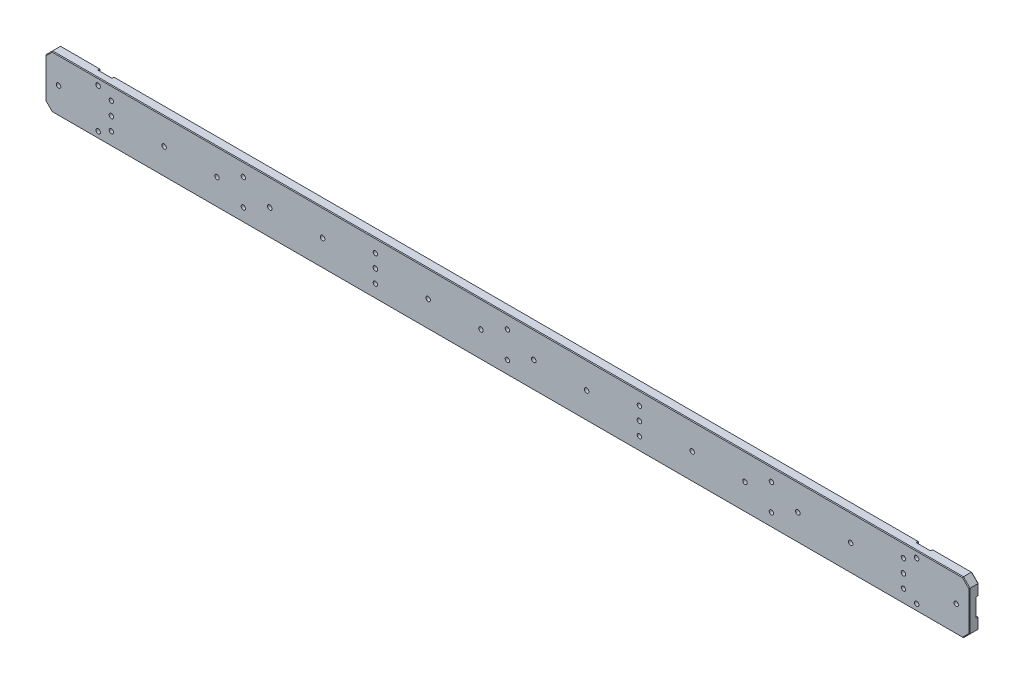
SolidWorks part; units mm, degrees
ref_plane "前视基准面" through (0, 0, 0) normal (0, 0, 1) x (1, 0, 0)
ref_plane "上视基准面" through (0, 0, 0) normal (0, 1, 0) x (1, 0, 0)
ref_plane "右视基准面" through (0, 0, 0) normal (1, 0, 0) x (0, 0, -1)
sketch "草图1" plane through (0, 0, 0) normal (0, 0, 1) x (1, 0, 0)
  line L1 (-700, 40) -> (700, 40)
  line L2 (-700, 40) -> (-700, -40)
  line L3 (-700, -40) -> (700, -40)
  line L4 (700, 40) -> (700, -40)
  line L5 (-700, 40) -> (700, -40) construction
  line L6 (-700, -40) -> (700, 40) construction
  point P0 (0, 0)
  dimension "D1" = 1400
  dimension "D2" = 80
extrude "凸台-拉伸1" add sketch "草图1" along normal blind 14
sketch "草图2" plane through (0, 0, 0) normal (0, 0, -1) x (-1, 0, 0)
  line L1 (750, -14) -> (-750, -14)
  line L2 (750, -14) -> (750, 14)
  line L3 (750, 14) -> (-750, 14)
  line L4 (-750, -14) -> (-750, 14)
  line L5 (750, -14) -> (-750, 14) construction
  line L6 (750, 14) -> (-750, -14) construction
  point P0 (0, 0)
  dimension "D1" = 28
  dimension "D2" = 1500
extrude "切除-拉伸1" cut sketch "草图2" against normal blind 4
hole_wizard "打孔尺寸(%根据)内六角圆柱头螺钉的类型1" positions "草图4" profile "草图6" counterbore size "M6" standard "GB" end condition through all
sketch "草图4" plane through (0, 0, 0) normal (0, 0, -1) x (-1, 0, 0)
  line L0 (0, -20) -> (0, 20) construction
  point P0 (0, -20)
  point P1 (0, 20)
  point P4 (0, 0)
  dimension "D1" = 40
sketch "草图6" plane through (0, -20, 0) normal (1, 0, 0) x (0, 1, 0)
  line L0 (0, 0) -> (0, 14)
  line L1 (0, 14) -> (3.3, 14)
  line L3 (3.3, 14) -> (3.3, 8)
  line L4 (3.3, 8) -> (5.5, 8)
  line L5 (5.5, 8) -> (5.5, 0)
  line L7 (5.5, 0) -> (0, 0)
  line L11 (0, -6.35) -> (0, 107.95) construction
  dimension "通孔孔直径" = 6.6
  dimension "通孔孔深度" = 14
  dimension "柱形沉头孔直径" = 11
  dimension "柱形沉头孔深度" = 8
pattern_linear "阵列(线性)1" count 4 spacing 200 along (1, 0, 0) count 4 spacing 200 along (-1, 0, 0) of "打孔尺寸(%根据)内六角圆柱头螺钉的类型1"
hole_wizard "M8 螺纹孔1" positions "草图7" profile "草图8" tap size "M8" standard "GB" end condition through all
sketch "草图7" plane through (0, 0, 4) normal (0, 0, -1) x (-1, 0, 0)
  point P0 (-680, 0)
sketch "草图8" plane through (680, 0, 4) normal (1, 0, 0) x (0, 1, 0)
  line L0 (0, 0) -> (0, 10)
  line L1 (0, 10) -> (3.4, 10)
  line L2 (3.4, 10) -> (3.4, 0)
  line L5 (3.4, 0) -> (0, 0)
  line L11 (0, -6.35) -> (0, 107.95) construction
  dimension "通孔螺纹孔钻头直径" = 6.8
  dimension "通孔螺纹孔钻头深度" = 10
cosmetic thread "孔螺蚊线1" parameters "D2"=8
pattern_linear "阵列(线性)2" count 18 spacing 80 along (-1, 0, 0) of "M8 螺纹孔1"
cosmetic thread "孔螺蚊线2" parameters "D2"=8
cosmetic thread "孔螺蚊线3" parameters "D2"=8
cosmetic thread "孔螺蚊线4" parameters "D2"=8
cosmetic thread "孔螺蚊线5" parameters "D2"=8
cosmetic thread "孔螺蚊线6" parameters "D2"=8
cosmetic thread "孔螺蚊线7" parameters "D2"=8
cosmetic thread "孔螺蚊线8" parameters "D2"=8
cosmetic thread "孔螺蚊线9" parameters "D2"=8
cosmetic thread "孔螺蚊线10" parameters "D2"=8
cosmetic thread "孔螺蚊线11" parameters "D2"=8
cosmetic thread "孔螺蚊线12" parameters "D2"=8
cosmetic thread "孔螺蚊线13" parameters "D2"=8
cosmetic thread "孔螺蚊线14" parameters "D2"=8
cosmetic thread "孔螺蚊线15" parameters "D2"=8
cosmetic thread "孔螺蚊线16" parameters "D2"=8
cosmetic thread "孔螺蚊线17" parameters "D2"=8
cosmetic thread "孔螺蚊线18" parameters "D2"=8
chamfer "倒角1" distance 10 angle 45 4 edges at (-700, -40, 7) (-700, 40, 7) (700, -40, 7) (700, 40, 7)
chamfer "倒角2" distance 1 angle 45 20 edges at (695, 35, 14) (0, 40, 14) (-695, 35, 14) (-700, 0, 14) (-695, -35, 14) (0, -40, 14) (695, -35, 14) (700, 0, 14) (695, -35, 0) (700, -22, 0) (0, -40, 0) (-695, -35, 0) (-700, -22, 0) (0, -14, 0) (-695, 35, 0) (-700, 22, 0) (0, 14, 0) (700, 22, 0) (695, 35, 0) (0, 40, 0)
sketch "草图9" plane through (0, -40, 0) normal (0, -1, 0) x (1, 0, 0)
  line L0 (689.5858, 0) -> (-689.5858, 0) construction
  line L1 (-610, -3) -> (-630, -3)
  line L2 (-610, -3) -> (-610, 3)
  line L3 (-610, 3) -> (-630, 3)
  line L4 (-630, -3) -> (-630, 3)
  line L5 (-610, -3) -> (-630, 3) construction
  line L6 (-610, 3) -> (-630, -3) construction
  line L7 (-700, 1) -> (-700, 13) construction
  point P0 (-620, 0)
  dimension "D1" = 20
  dimension "D2" = 70
  dimension "D3" = 3
extrude "切除-拉伸2" cut sketch "草图9" against normal through all
hole_wizard "M8 螺纹孔2" positions "草图10" profile "草图11" tap size "M8" standard "GB" end condition through all
sketch "草图10" plane through (0, 0, 3) normal (0, 0, -1) x (-1, 0, 0)
  point P0 (620, -30)
  point P2 (620, 30)
sketch "草图11" plane through (-620, -30, 3) normal (1, 0, 0) x (0, 1, 0)
  line L0 (0, 0) -> (0, 11)
  line L1 (0, 11) -> (3.4, 11)
  line L2 (3.4, 11) -> (3.4, 0)
  line L5 (3.4, 0) -> (0, 0)
  line L11 (0, -6.35) -> (0, 107.95) construction
  dimension "通孔螺纹孔钻头直径" = 6.8
  dimension "通孔螺纹孔钻头深度" = 11
cosmetic thread "孔螺蚊线19" parameters "D2"=8
cosmetic thread "孔螺蚊线20" parameters "D2"=8
mirror "镜向1" about plane through (0, 0, 0) normal (1, 0, 0) of "M8 螺纹孔2", "切除-拉伸2"
cosmetic thread "孔螺蚊线21" parameters "D2"=8
cosmetic thread "孔螺蚊线22" parameters "D2"=8
chamfer "倒角3" distance 1 angle 45 48 edges at (-610, 39.5, 0.5) (-610, 40, 2) (-620, 40, 3) (-630, 40, 2) (-630, 39.5, 0.5) (-630, 27, 0) (-630, 14.5, 0.5) (-630, 14, 2) (-620, 14, 3) (-610, 14, 2) (-610, 14.5, 0.5) (-610, 27, 0) (-610, -14.5, 0.5) (-610, -14, 2) (-620, -14, 3) (-630, -14, 2) (-630, -14.5, 0.5) (-630, -27, 0) (-630, -39.5, 0.5) (-630, -40, 2) (-620, -40, 3) (-610, -40, 2) (-610, -39.5, 0.5) (-610, -27, 0) (610, 14, 2) (610, 14.5, 0.5) (610, 27, 0) (610, 39.5, 0.5) (610, 40, 2) (620, 40, 3) (630, 40, 2) (630, 39.5, 0.5) (620, 14, 3) (630, 14, 2) (630, 14.5, 0.5) (630, 27, 0) (610, -39.5, 0.5) (610, -40, 2) (610, -27, 0) (610, -14.5, 0.5) (610, -14, 2) (620, -14, 3) (630, -14, 2) (630, -14.5, 0.5) (620, -40, 3) (630, -40, 2) (630, -39.5, 0.5) (630, -27, 0)
